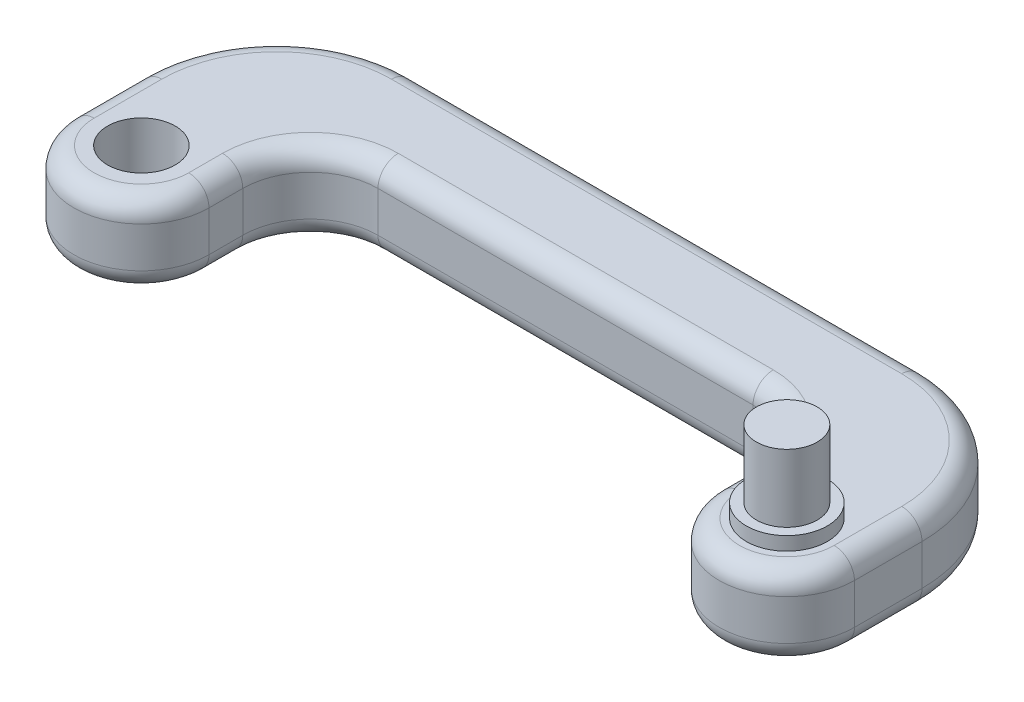
SolidWorks part; units mm, degrees
ref_plane "Front Plane" through (0, 0, 0) normal (0, 0, 1) x (1, 0, 0)
ref_plane "Top Plane" through (0, 0, 0) normal (0, 1, 0) x (1, 0, 0)
ref_plane "Right Plane" through (0, 0, 0) normal (1, 0, 0) x (0, 0, -1)
sketch "Sketch7" plane through (0, 0, 0) normal (0, 1, 0) x (1, 0, 0)
  line L2 (-105.5, 0) -> (-105.5, 30)
  line L3 (-85.5, 0) -> (-85.5, 15)
  line L4 (-105.5, 30) -> (-85.5, 30)
  line L6 (-85.5, 30) -> (10, 30)
  line L7 (-85.5, 15) -> (-10, 15)
  line L10 (10, 0) -> (10, 30.0013)
  line L11 (-10, 0) -> (-10, 15)
  line L12 (10, 30.0013) -> (-10, 30.0013)
  line L13 (-10, 30) -> (-10, 30.0013)
  arc A0 (-10, 0) -> (10, 0) centre (0, 0) ccw
  arc A1 (-105.5, 0) -> (-85.5, 0) centre (-95.5, 0) ccw
  circle A2 centre (-95.5, 0) radius 5
extrude "Boss-Extrude5" add sketch "Sketch7" along normal blind 12 contours L2 A1 L3 L7 L11 A0 L10 L6 L4 A2 region at (-46.2897, 0, -16.412)
sketch "Sketch8" plane through (0, 12, 0) normal (0, 1, 0) x (1, 0, 0)
  circle A0 centre (0, 0) radius 6
extrude "Boss-Extrude6" add sketch "Sketch8" along normal blind 2 contours A0
sketch "Sketch9" plane through (0, 14, 0) normal (0, 1, 0) x (1, 0, 0)
  circle A0 centre (0, 0) radius 4.5
extrude "Boss-Extrude7" add sketch "Sketch9" along normal blind 10
fillet "Fillet2" radius 20 2 edges at (10, 6, -30) (-105.5, 6, -30)
fillet "Fillet3" radius 10 2 edges at (-10, 6, -15) (-85.5, 6, -15)
fillet "Fillet5" radius 3 24 edges at (-47.75, 12, -30) (4.1421, 12, -24.1421) (10, 12, -5) (0, 12, 10) (-10, 12, -2.5) (-12.9289, 12, -12.0711) (-47.75, 12, -15) (-82.5711, 12, -12.0711) (-85.5, 12, -2.5) (-95.5, 12, 10) (-105.5, 12, -5) (-105.5, 0, -5) (-95.5, 0, 10) (-85.5, 0, -2.5) (-82.5711, 0, -12.0711) (-47.75, 0, -15) (-12.9289, 0, -12.0711) (-10, 0, -2.5) (0, 0, 10) (10, 0, -5) (4.1421, 0, -24.1421) (-47.75, 0, -30) (-99.6421, 12, -24.1421) (-99.6421, 0, -24.1421)
sketch "Sketch10" plane through (0, 12, 0) normal (0, 1, 0) x (1, 0, 0)
  circle A0 centre (-95.5, 0) radius 5.1
